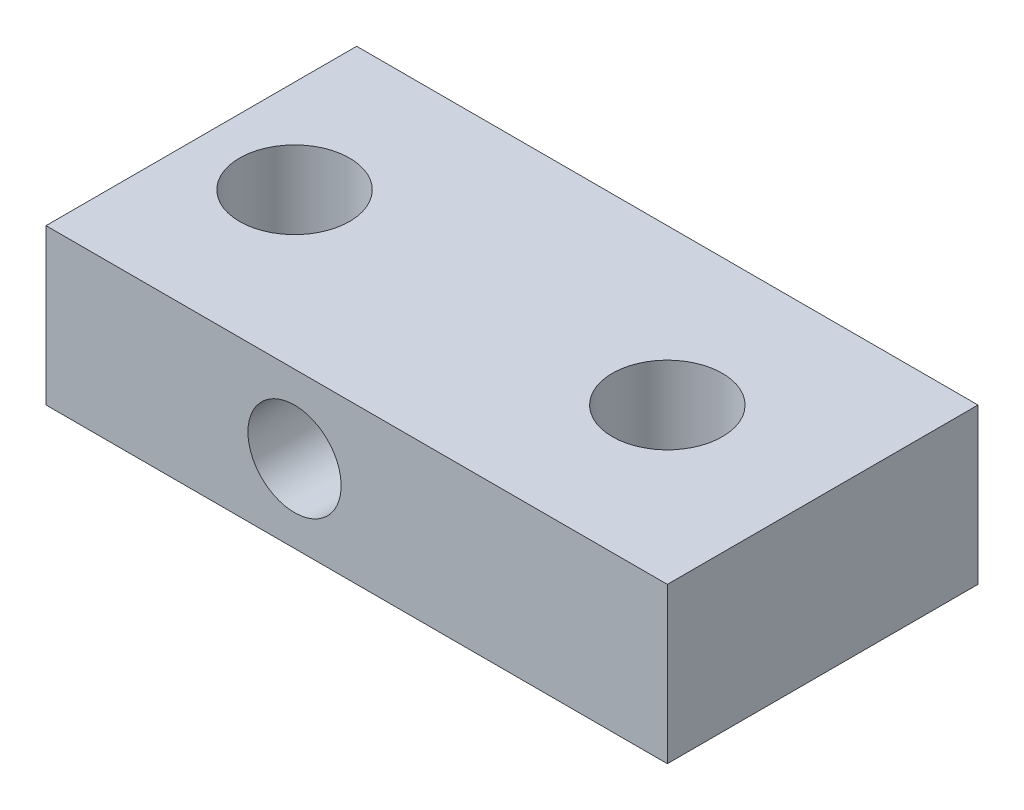
SolidWorks part; units mm, degrees
ref_plane "Front Plane" through (0, 0, 0) normal (0, 0, 1) x (1, 0, 0)
ref_plane "Top Plane" through (0, 0, 0) normal (0, 1, 0) x (1, 0, 0)
ref_plane "Right Plane" through (0, 0, 0) normal (1, 0, 0) x (0, 0, -1)
sketch "Sketch1" plane through (0, 0, 0) normal (0, 1, 0) x (1, 0, 0)
  line L1 (-12.7, -6.35) -> (12.7, -6.35)
  line L2 (-12.7, -6.35) -> (-12.7, 6.35)
  line L3 (-12.7, 6.35) -> (12.7, 6.35)
  line L4 (12.7, -6.35) -> (12.7, 6.35)
  line L5 (-12.7, -6.35) -> (12.7, 6.35) construction
  line L6 (-12.7, 6.35) -> (12.7, -6.35) construction
  point P0 (0, 0)
  dimension "D1" = 25.4
  dimension "D2" = 12.7
extrude "Boss-Extrude1" add sketch "Sketch1" along normal blind 6.35
sketch "Sketch2" plane through (0, 0, -6.35) normal (0, 0, -1) x (-1, 0, 0)
  line L0 (-12.7, 6.35) -> (-12.7, 0) construction
  circle A0 centre (2.54, 3.175) radius 1.905
  point P3 (-12.7, 3.175)
  dimension "D1" = 3.81
  dimension "D2" = 2.54
extrude "Cut-Extrude1" cut sketch "Sketch2" against normal through all contours A0
hole_wizard "#8 Clearance Hole1" positions "Sketch3" profile "Sketch4" hole size "#8" standard "ANSI Inch" end condition through all
sketch "Sketch3" plane through (0, 6.35, 0) normal (0, 1, 0) x (1, 0, 0)
  line L0 (-8.89, 0) -> (6.35, 0) construction
  line L1 (-12.7, 6.35) -> (-12.7, -6.35) construction
  point P1 (-8.89, 0)
  point P2 (6.35, 0)
  point P8 (-8.89, 0)
  point P12 (6.35, 0)
  point P16 (-12.7, 0)
  dimension "D1" = 15.24
  dimension "D2" = 3.81
sketch "Sketch4" plane through (6.35, 6.35, 0) normal (1, 0, 0) x (0, 0, 1)
  line L0 (0, 0) -> (0, 6.35)
  line L1 (0, 6.35) -> (2.2479, 6.35)
  line L2 (2.2479, 6.35) -> (2.2479, 0)
  line L5 (2.2479, 0) -> (0, 0)
  line L11 (0, -6.35) -> (0, 107.95) construction
  dimension "Thru Hole Dia." = 4.4958
  dimension "Thru Hole Depth" = 6.35
